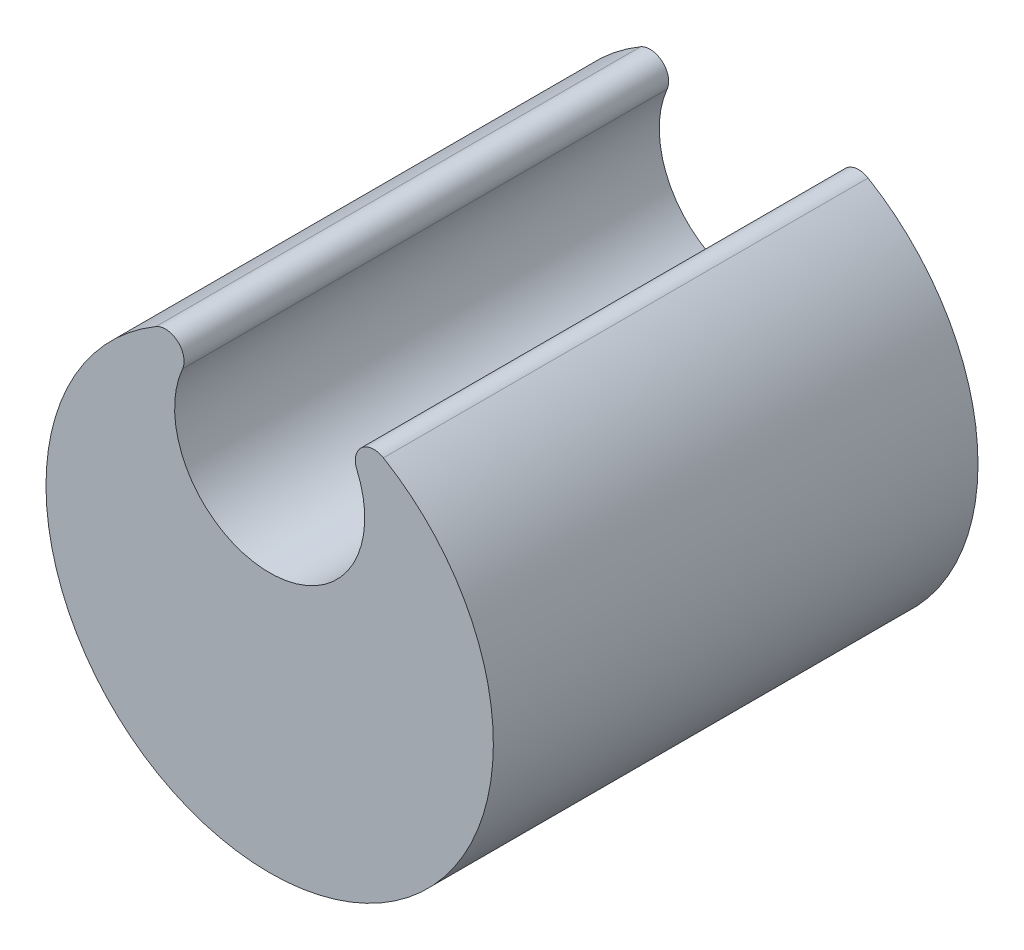
SolidWorks part; units mm, degrees
ref_plane "Front" through (0, 0, 0) normal (0, 0, 1) x (1, 0, 0)
ref_plane "Top" through (0, 0, 0) normal (0, 1, 0) x (1, 0, 0)
ref_plane "Right" through (0, 0, 0) normal (1, 0, 0) x (0, 0, -1)
sketch "Skizze1" plane through (0, 0, 0) normal (0, 0, 1) x (1, 0, 0)
  line L0 (0, 0) -> (0, 7.2203) construction
  circle A0 centre (0, 0) radius 6
  circle A1 centre (0, 3.5198) radius 2.55
  dimension "D1" = 12
  dimension "D2" = 5.1
extrude "Aufsatz-Linear austragen2" add sketch "Skizze1" along normal blind 13 contours A1 A0 region at (0, -0.7706, 0)
fillet "Verrundung1" radius 0.5 2 edges at (0.7718, 5.9502, 6.5) (-0.7718, 5.9502, 6.5)
